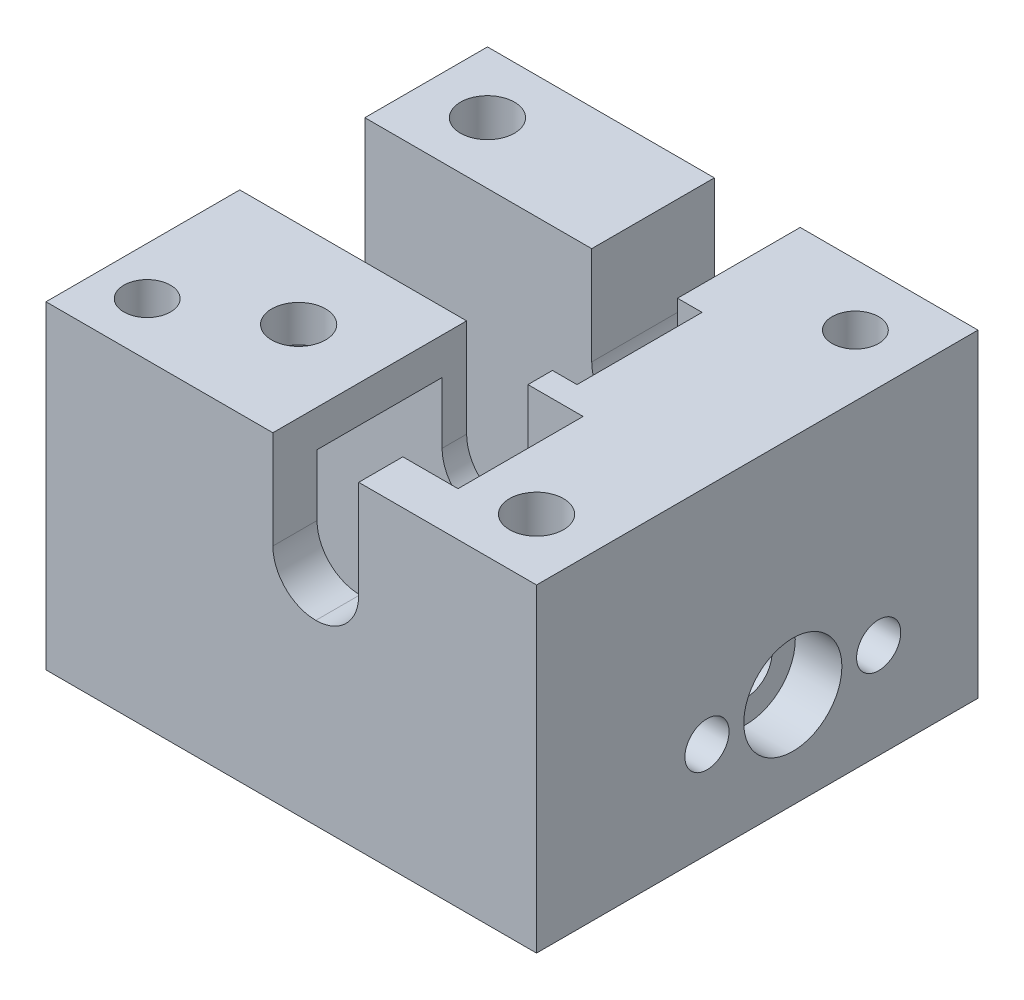
SolidWorks part; units mm, degrees
ref_plane "Front" through (0, 0, 0) normal (0, 0, 1) x (1, 0, 0)
ref_plane "Top" through (0, 0, 0) normal (0, 1, 0) x (1, 0, 0)
ref_plane "Right" through (0, 0, 0) normal (1, 0, 0) x (0, 0, -1)
sketch "Sketch1" plane through (0, 0, 0) normal (0, 1, 0) x (1, 0, 0)
  line L1 (-10, -9) -> (10, -9)
  line L2 (-10, -9) -> (-10, 9)
  line L3 (-10, 9) -> (10, 9)
  line L4 (10, -9) -> (10, 9)
  line L5 (-10, -9) -> (10, 9) construction
  line L6 (-10, 9) -> (10, -9) construction
  point P0 (0, 0)
  dimension "D1" = 20
  dimension "D2" = 18
extrude "Boss-Extrude1" add sketch "Sketch1" along normal blind 13
sketch "Sketch7" plane through (0, 0, 9) normal (0, 0, 1) x (1, 0, 0)
  line L0 (-10, 13) -> (10, 13) construction
  line L1 (-0.75, 13) -> (2.75, 13)
  line L2 (-0.75, 13) -> (-0.75, 7.25)
  line L3 (-0.75, 7.25) -> (2.75, 7.25)
  line L4 (2.75, 13) -> (2.75, 7.25)
  line L5 (-10, 13) -> (-10, 0) construction
  line L7 (1, 9) -> (1, 7.25) construction
  line L8 (1, 9) -> (-0.75, 9) construction
  dimension "D1" = 3.5
  dimension "D2" = 11
  dimension "D3" = 4
extrude "Cut-Extrude6" cut sketch "Sketch7" against normal through all
sketch "Sketch2" plane through (-10, 0, 0) normal (-1, 0, 0) x (0, 0, 1)
  line L0 (-9, 13) -> (9, 13) construction
  line L1 (1.1, 13) -> (-4, 13)
  line L2 (1.1, 13) -> (1.1, 1.9)
  line L3 (1.1, 1.9) -> (-4, 1.9)
  line L4 (-4, 13) -> (-4, 1.9)
  line L7 (-9, 13) -> (-9, 0) construction
  dimension "D1" = 11.1
  dimension "D2" = 5.1
  dimension "D3" = 5
extrude "Cut-Extrude1" cut sketch "Sketch2" against normal offset from surface (13.75 mm away) 1 up to face at (2.75, 10.125, 0) offset beyond the face yes
sketch "Sketch3" plane through (3.75, 0, 0) normal (-1, 0, 0) x (0, 0, 1)
  line L0 (-1.45, 1.9) -> (-1.45, 3.9) construction
  line L1 (-4, 1.9) -> (1.1, 1.9) construction
  circle A0 centre (-1.45, 3.9) radius 1.05
  dimension "D1" = 2.1
  dimension "D2" = 2
extrude "Cut-Extrude2" cut sketch "Sketch3" against normal through all
sketch "Sketch4" plane through (10, 0, 0) normal (1, 0, 0) x (0, 0, -1)
  circle A0 centre (1.45, 3.9) radius 2
  dimension "D1" = 4
extrude "Cut-Extrude3" cut sketch "Sketch4" against normal blind 1.9
sketch "Sketch11" plane through (10, 0, 0) normal (1, 0, 0) x (0, 0, -1)
  line L0 (1.45, 3.9) -> (1.45, 0) construction
  line L1 (-9, 0) -> (9, 0) construction
  line L2 (1.45, 3.9) -> (4.95, 3.9) construction
  circle A0 centre (4.95, 3.9) radius 0.9
  circle A1 centre (-2.05, 3.9) radius 0.9
  dimension "D1" = 1.8
  dimension "D2" = 7
extrude "Cut-Extrude9" cut sketch "Sketch11" against normal blind 3
sketch "Sketch5" plane through (0, 13, 0) normal (0, 1, 0) x (1, 0, 0)
  line L0 (3.75, -1.1) -> (2.75, -1.1) construction
  line L1 (-6.1, -2.1) -> (5, -2.1)
  line L2 (-6.1, -2.1) -> (-6.1, -7.2)
  line L3 (-6.1, -7.2) -> (5, -7.2)
  line L4 (5, -2.1) -> (5, -7.2)
  line L5 (1, 9) -> (1, -9) construction
  line L7 (-0.75, -9) -> (2.75, -9) construction
  line L8 (5, -4.65) -> (1, -4.65) construction
  line L9 (-0.75, 9) -> (2.75, 9) construction
  dimension "D1" = 11.1
  dimension "D2" = 5.1
  dimension "D3" = 1
  dimension "D4" = 4
extrude "Cut-Extrude4" cut sketch "Sketch5" against normal through all
sketch "Sketch8" plane through (0, 13, 0) normal (0, 1, 0) x (1, 0, 0)
  line L0 (-6.1, -4.65) -> (-4.05, -4.65) construction
  line L1 (-6.1, -2.1) -> (-0.75, -2.1)
  line L2 (-6.1, -2.1) -> (-6.1, -7.2)
  line L3 (-6.1, -7.2) -> (-0.75, -7.2)
  line L4 (-0.75, -2.1) -> (-0.75, -7.2)
  circle A0 centre (-4.05, -4.65) radius 1.1
  dimension "D2" = 2.2
  dimension "D1" = 2.05
extrude "Boss-Extrude2" add sketch "Sketch8" against normal blind 1.5
sketch "Sketch10" plane through (0, 13, 0) normal (0, 1, 0) x (1, 0, 0)
  line L0 (-6.1, -2.1) -> (-6.1, -7.2) construction
  line L1 (-10, -9) -> (-6.1, -4.65) construction
  line L5 (-10, 9) -> (-10, -9) construction
  line L7 (7.5, 9) -> (7.5, 6.5) construction
  line L8 (10, 9) -> (2.75, 9) construction
  line L9 (7.5, 6.5) -> (10, 6.5) construction
  line L10 (-6.1, -2.1) -> (-6.1, -7.2) construction
  line L12 (-10, 6.5) -> (7.5, 6.5) construction
  line L14 (-10, 9) -> (-10, 4) construction
  line L15 (10, -9) -> (10, 9) construction
  circle A0 centre (-8.05, -6.825) radius 0.95
  circle A5 centre (7.5, 6.5) radius 0.95
  dimension "D1" = 1.9
extrude "Cut-Extrude8" cut sketch "Sketch10" against normal blind 6
sketch "Sketch14" plane through (0, 13, 0) normal (0, 1, 0) x (1, 0, 0)
  line L0 (-7.5, 9) -> (-7.5, 6.5) construction
  line L2 (10, 9) -> (2.75, 9) construction
  line L3 (-7.5, 6.5) -> (-10, 6.5) construction
  line L4 (-10, 9) -> (-10, 4) construction
  line L5 (7.5, -6.5) -> (10, -6.5) construction
  line L6 (10, -9) -> (10, 9) construction
  line L7 (7.5, -6.5) -> (7.5, -9) construction
  line L8 (2.75, -9) -> (10, -9) construction
  circle A0 centre (-7.5, 6.5) radius 1.1
  circle A1 centre (7.5, -6.5) radius 1.1
  dimension "D1" = 2.2
  dimension "D2" = 2.5
extrude "Cut-Extrude11" cut sketch "Sketch14" against normal through all
fillet "Fillet2" radius 1.75 6 edges at (2.75, 7.25, 8.1) (2.75, 7.25, 1.6) (-0.75, 7.25, 8.1) (-0.75, 7.25, 1.6) (2.75, 7.25, -6.5) (-0.75, 7.25, -6.5)
chamfer "Chamfer1" distance 0.5 angle 45 4 edges at (-6.1, 0, 4.65) (-0.55, 0, 2.1) (5, 0, 4.65) (-0.55, 0, 7.2)
